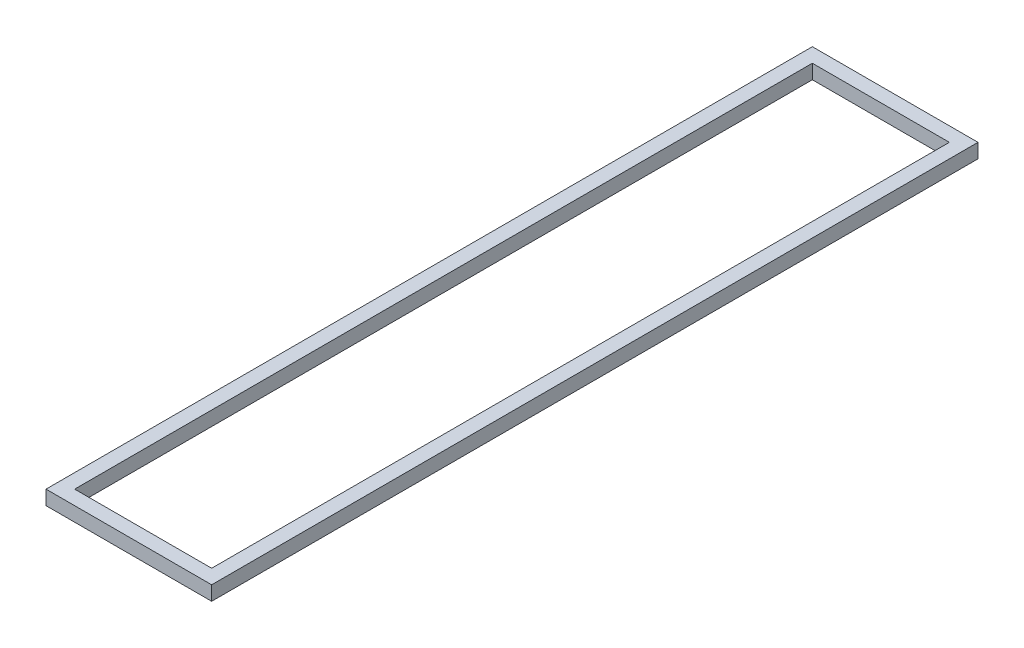
SolidWorks part; units mm, degrees
ref_plane "Front Plane" through (0, 0, 0) normal (0, 0, 1) x (1, 0, 0)
ref_plane "Top Plane" through (0, 0, 0) normal (0, 1, 0) x (1, 0, 0)
ref_plane "Right Plane" through (0, 0, 0) normal (1, 0, 0) x (0, 0, -1)
sketch "Sketch1" plane through (0, 0, 0) normal (0, 1, 0) x (1, 0, 0)
  line L1 (-70.1988, 1301.5067) -> (223.5522, 1301.5067)
  line L2 (-70.1988, 1301.5067) -> (-70.1988, -57.3933)
  line L3 (-70.1988, -57.3933) -> (223.5522, -57.3933)
  line L4 (223.5522, 1301.5067) -> (223.5522, -57.3933)
  line L5 (-44.7988, 1276.1067) -> (198.1522, 1276.1067)
  line L6 (-44.7988, 1276.1067) -> (-44.7988, -31.9933)
  line L7 (-44.7988, -31.9933) -> (198.1522, -31.9933)
  line L8 (198.1522, 1276.1067) -> (198.1522, -31.9933)
  dimension "D1" = 25.4
  dimension "D2" = 25.4
  dimension "D3" = 25.4
  dimension "D4" = 25.4
  dimension "D5" = 293.751
  dimension "D6" = 1358.9
extrude "Extrude1" add sketch "Sketch1" along normal blind 25.4
sketch "Sketch2" plane through (0, 0, 57.3933) normal (0, 0, 1) x (1, 0, 0)
  line L0 (-70.1988, 25.4) -> (223.5522, 25.4) construction
  line L1 (223.5522, 25.4) -> (223.5522, 0) construction
  point P0 (210.8522, 12.7)
  dimension "D1" = 12.7
  dimension "D2" = 12.7
ref_axis "Glide Axis" through (210.8522, 12.7, 57.3933) along (0, 0, 1)
sketch "Sketch3" plane through (0, 0, 57.3933) normal (0, 0, 1) x (1, 0, 0)
  line L0 (-70.1988, 25.4) -> (-70.1988, 0) construction
  point P0 (-70.9862, 25.4)
  dimension "D1" = 0.7874
ref_axis "Hinge Axis" through (-70.9862, 25.4, 57.3933) along (0, 0, 1)
